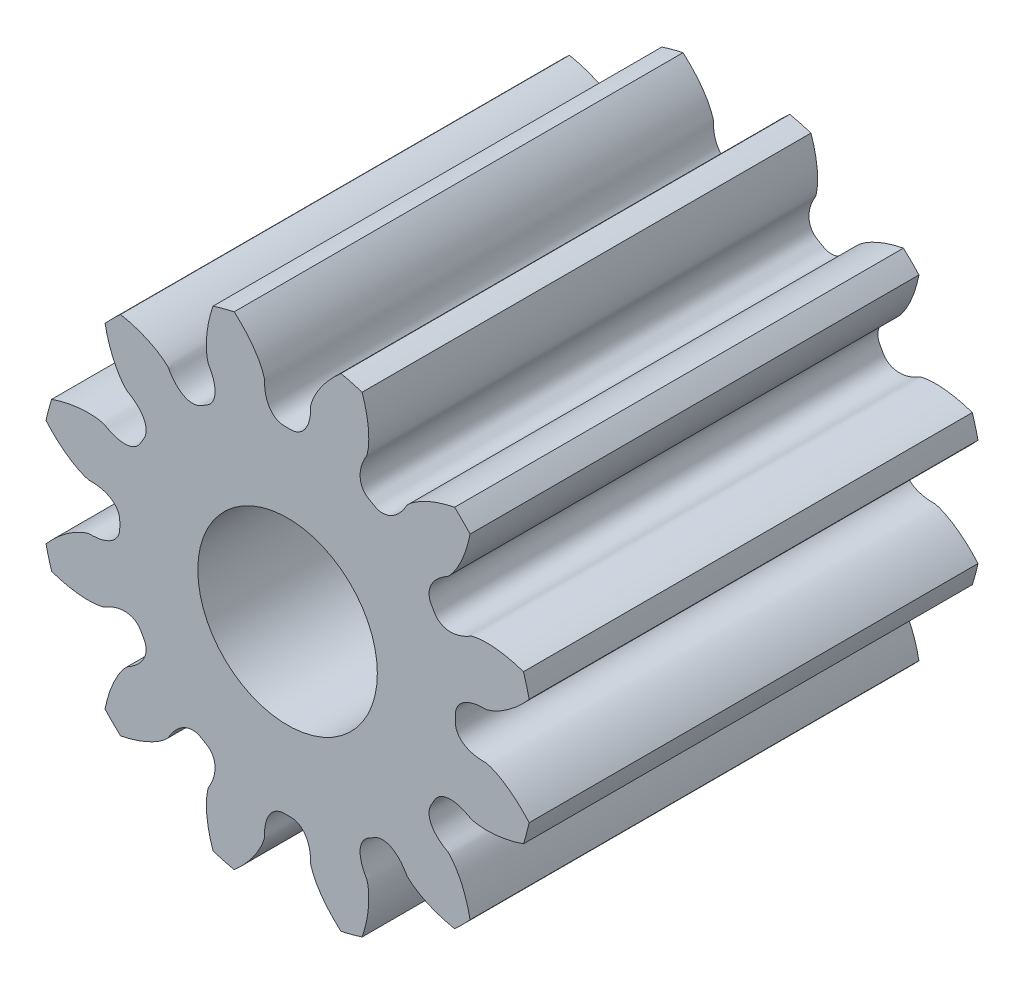
SolidWorks part; units mm, degrees
ref_plane "Front Plane" through (0, 0, 0) normal (0, 0, 1) x (1, 0, 0)
ref_plane "Top Plane" through (0, 0, 0) normal (0, 1, 0) x (1, 0, 0)
ref_plane "Right Plane" through (0, 0, 0) normal (1, 0, 0) x (0, 0, -1)
ref_axis "Axis1" through (0, 0, 55) along (0, 0, -1)
sketch "SketchRevolveSpur01" plane through (0, 0, 0) normal (1, 0, 0) x (0, 0, -1)
  line L0 (0, 0) -> (25.4, 0) construction
  line L1 (-6.35, 0) -> (-6.35, 7)
  line L2 (-6.35, 7) -> (6.35, 7)
  line L3 (6.35, 7) -> (6.35, 0)
  line L4 (6.35, 0) -> (-6.35, 0)
  dimension "Side1" = 6.35
  dimension "OutsideRadius" = 7
  dimension "Side2" = 6.35
revolve "Spur01" add sketch "SketchRevolveSpur01" angle 360 about L0
sketch "SketchToothSpur01" plane through (0, 0, 0) normal (0, 0, 1) x (1, 0, 0)
  arc A0 (6.8758, 1.5574) -> (6.8758, -1.5574) centre (0, 0) cw
  spline S0 degree 3 poles (6.8758, -1.5574) (6.842, -1.5184) (6.7761, -1.4424) (6.6746, -1.336) (6.5752, -1.2388) (6.478, -1.1509) (6.3837, -1.0717) (6.2927, -1.001) (6.2057, -0.9384) (6.1229, -0.8835) (6.045, -0.8358) (5.9722, -0.795) (5.905, -0.7606) (5.8438, -0.7321) (5.7889, -0.7089) (5.7406, -0.6907) (5.6992, -0.6767) (5.6586, -0.6652) (5.6072, -0.65) (5.5479, -0.6574) (5.4881, -0.6536) (5.437, -0.6502) (5.3873, -0.6448) (5.339, -0.6378) (5.292, -0.6291) (5.2465, -0.6187) (5.2023, -0.6067) (5.1595, -0.5929) (5.1179, -0.5773) (5.0777, -0.5598) (5.0388, -0.5403) (5.0012, -0.5185) (4.965, -0.4945) (4.9302, -0.4678) (4.897, -0.4381) (4.8657, -0.4053) (4.8365, -0.3689) (4.8102, -0.3288) (4.7874, -0.2848) (4.7689, -0.2371) (4.7557, -0.1862) (4.7497, -0.1383) (4.7472, -0.076) (4.7506, 0) (4.7472, 0.076) (4.7497, 0.1383) (4.7557, 0.1862) (4.7689, 0.2371) (4.7874, 0.2848) (4.8102, 0.3288) (4.8365, 0.3689) (4.8657, 0.4053) (4.897, 0.4381) (4.9302, 0.4678) (4.965, 0.4945) (5.0012, 0.5185) (5.0388, 0.5403) (5.0777, 0.5598) (5.1179, 0.5773) (5.1595, 0.5929) (5.2023, 0.6067) (5.2465, 0.6187) (5.292, 0.6291) (5.339, 0.6378) (5.3873, 0.6448) (5.437, 0.6502) (5.4881, 0.6536) (5.5479, 0.6574) (5.6072, 0.65) (5.6586, 0.6652) (5.6992, 0.6767) (5.7406, 0.6907) (5.7889, 0.7089) (5.8438, 0.7321) (5.905, 0.7606) (5.9722, 0.795) (6.045, 0.8358) (6.1229, 0.8835) (6.2057, 0.9384) (6.2927, 1.001) (6.3837, 1.0717) (6.478, 1.1509) (6.5752, 1.2388) (6.6746, 1.336) (6.7761, 1.4424) (6.842, 1.5184) (6.8758, 1.5574) knots 0 0 0 0 0.027444 0.053481 0.07811 0.101332 0.123147 0.143554 0.162553 0.180146 0.196331 0.211108 0.224479 0.236441 0.246997 0.256145 0.263886 0.270219 0.278621 0.292086 0.301392 0.310467 0.319322 0.327967 0.336416 0.344685 0.352792 0.360757 0.368603 0.376359 0.384055 0.391727 0.399416 0.407167 0.415027 0.423048 0.431277 0.439759 0.448521 0.45757 0.466888 0.47642 0.483158 0.5 0.516842 0.52358 0.533112 0.54243 0.551479 0.560241 0.568723 0.576952 0.584973 0.592833 0.600584 0.608273 0.615945 0.623641 0.631397 0.639243 0.647208 0.655315 0.663584 0.672033 0.680678 0.689533 0.698608 0.707914 0.721379 0.729781 0.736114 0.743855 0.753003 0.763559 0.775521 0.788892 0.803669 0.819854 0.837447 0.856446 0.876853 0.898668 0.92189 0.946519 0.972556 1 1 1 1
extrude "ToothExtrudeCutSpur01" cut sketch "SketchToothSpur01" against normal blind 9.525 and the other way blind 9.525
pattern_circular "PatternSpur01" count 12 every 30 about axis through (0, 0, 55) along (0, 0, -1) of "ToothExtrudeCutSpur01"
sketch "BoreRevolveSketch" plane through (0, 0, 0) normal (1, 0, 0) x (0, 0, -1)
  line L0 (0, 0) -> (25.4, 0) construction
  line L1 (-9.525, 0) -> (9.525, 0)
  line L2 (9.525, 0) -> (9.525, 2.794)
  line L3 (9.525, 2.794) -> (9.271, 2.54)
  line L4 (9.271, 2.54) -> (-9.271, 2.54)
  line L5 (-9.271, 2.54) -> (-9.525, 2.794)
  line L6 (-9.525, 2.794) -> (-9.525, 0)
  dimension "BoreSide1" = 9.525
  dimension "TaperSide1" = 2.794
  dimension "Chamfer1X" = 0.254
  dimension "Chamfer1Y" = 0.254
  dimension "BoreSide2" = 9.525
  dimension "TaperSide2" = 2.794
revolve "BoreRevolveCut" cut sketch "BoreRevolveSketch" angle 360 about L0
sketch "AuxiliarySketchSpur01" plane through (0, 0, 0) normal (0, 0, 1) x (1, 0, 0)
  circle A0 centre (0, 0) radius 6 construction
  circle A1 centre (0, 0) radius 5.6382 construction
  circle A2 centre (0, 0) radius 5.7063 construction
  circle A3 centre (0, 0) radius 7 construction
  circle A4 centre (0, 0) radius 4.7492 construction
  dimension "PitchDiameter" = 12
  dimension "BaseDiameter" = 11.2763
  dimension "FormDiameter" = 11.4126
  dimension "MajorDiameter" = 14
  dimension "MinorDiameter" = 9.4984
